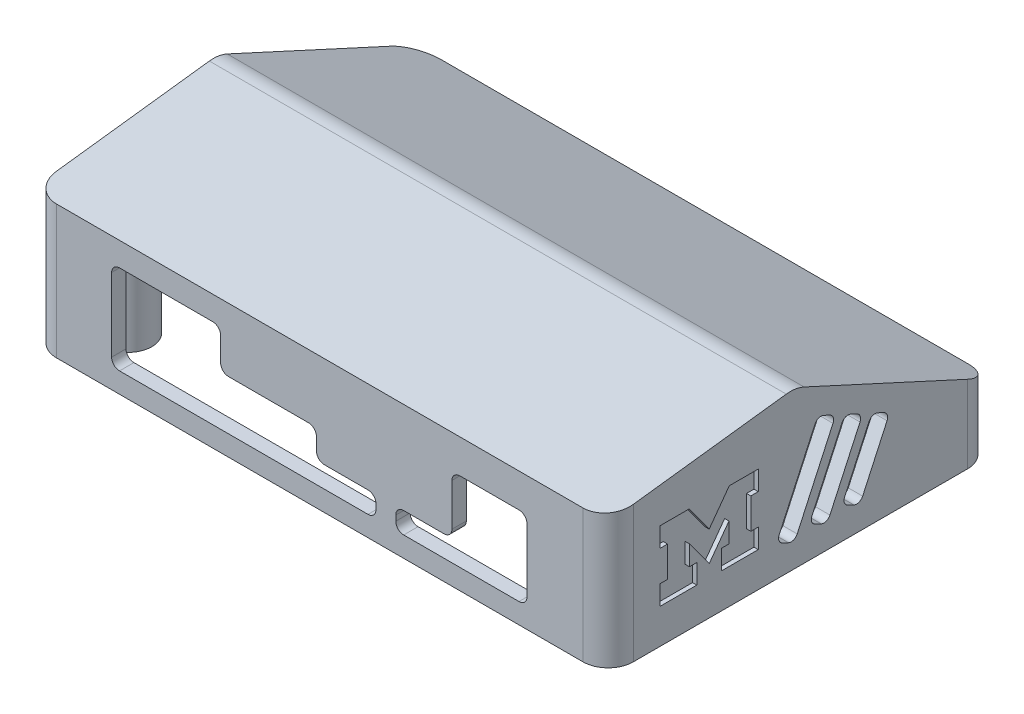
SolidWorks part; units mm, degrees
ref_plane "Front Plane" through (0, 0, 0) normal (0, 0, 1) x (1, 0, 0)
ref_plane "Top Plane" through (0, 0, 0) normal (0, 1, 0) x (1, 0, 0)
ref_plane "Right Plane" through (0, 0, 0) normal (1, 0, 0) x (0, 0, -1)
sketch "Sketch1" plane through (0, 0, 0) normal (0, 1, 0) x (1, 0, 0)
  line L0 (-37.7767, 21.1111) -> (-37.7767, -27.7389)
  line L1 (-34.6167, 23.6111) -> (43.3333, 23.6111)
  line L2 (-37.1167, 21.1111) -> (-37.1167, -27.7389)
  line L3 (-34.6167, -30.2389) -> (43.3333, -30.2389)
  line L4 (45.8333, 21.1111) -> (45.8333, -27.7389)
  line L5 (-34.6167, -30.8989) -> (43.3333, -30.8989)
  line L6 (46.4933, 21.1111) -> (46.4933, -27.7389)
  line L7 (-34.6167, 24.2711) -> (43.3333, 24.2711)
  arc A0 (-37.1167, -27.7389) -> (-34.6167, -30.2389) centre (-34.6167, -27.7389) ccw
  arc A1 (43.3333, -30.2389) -> (45.8333, -27.7389) centre (43.3333, -27.7389) ccw
  arc A2 (43.3333, 23.6111) -> (45.8333, 21.1111) centre (43.3333, 21.1111) cw
  arc A3 (-34.6167, 23.6111) -> (-37.1167, 21.1111) centre (-34.6167, 21.1111) ccw
  arc A4 (-37.7767, -27.7389) -> (-34.6167, -30.8989) centre (-34.6167, -27.7389) ccw
  arc A5 (43.3333, -30.8989) -> (46.4933, -27.7389) centre (43.3333, -27.7389) ccw
  arc A6 (43.3333, 24.2711) -> (46.4933, 21.1111) centre (43.3333, 21.1111) cw
  arc A7 (-34.6167, 24.2711) -> (-37.7767, 21.1111) centre (-34.6167, 21.1111) ccw
  point P8 (45.8333, -30.2389)
  point P11 (45.8333, 23.6111)
  point P14 (-37.1167, 23.6111)
  dimension "D3" = 2.5
  dimension "D1" = 82.95
  dimension "D2" = 53.85
  dimension "D4" = 0.66
extrude "Boss-Extrude1" add sketch "Sketch1" along normal blind 1.8
sketch "Sketch3" plane through (0, 1.8, 0) normal (0, 1, 0) x (1, 0, 0)
  line L8 (43.3333, 21.5611) -> (-34.6167, 21.5611)
  line L9 (-35.0667, 21.1111) -> (-35.0667, -27.7389)
  line L10 (-37.1167, 21.1111) -> (-37.1167, -27.7389)
  line L11 (-34.6167, -30.2389) -> (43.3333, -30.2389)
  line L33 (45.8333, -27.7389) -> (45.8333, 21.1111)
  line L34 (43.3333, 23.6111) -> (-34.6167, 23.6111)
  line L35 (-39.2917, 21.1111) -> (-39.2917, 25.7861)
  line L36 (-39.2917, 25.7861) -> (-34.6167, 25.7861)
  line L37 (43.3333, 25.7861) -> (-34.6167, 25.7861)
  line L38 (-39.2917, 21.1111) -> (-39.2917, -27.7389)
  line L39 (-34.6167, -32.4139) -> (43.3333, -32.4139)
  line L40 (48.0083, -27.7389) -> (48.0083, 21.1111)
  line L41 (43.3333, 25.7861) -> (-34.6167, 25.7861)
  line L42 (-39.2917, 21.1111) -> (-39.2917, -27.7389)
  line L43 (-34.6167, -32.4139) -> (43.3333, -32.4139)
  line L44 (48.0083, -27.7389) -> (48.0083, 21.1111)
  line L45 (-34.6167, 25.7861) -> (-34.5188, 25.7484)
  line L46 (48.0083, 21.1111) -> (48.0083, 25.7861)
  line L47 (48.0083, 25.7861) -> (43.3333, 25.7861)
  line L48 (43.3333, 25.7861) -> (43.4732, 25.7999)
  line L49 (48.0083, -27.7389) -> (48.0083, -32.4139)
  line L50 (48.0083, -32.4139) -> (43.3333, -32.4139)
  line L51 (-39.2917, -27.7389) -> (-39.2917, -32.4139)
  line L52 (-39.2917, -32.4139) -> (-34.6167, -32.4139)
  arc A6 (43.7833, 21.1111) -> (43.3333, 21.5611) centre (43.3333, 21.1111) ccw
  arc A7 (-34.6167, 21.5611) -> (-35.0667, 21.1111) centre (-34.6167, 21.1111) ccw
  arc A8 (43.7833, 21.1111) -> (43.3333, 21.5611) centre (43.3333, 21.1111) ccw
  arc A9 (-37.1167, -27.7389) -> (-34.6167, -30.2389) centre (-34.6167, -27.7389) ccw
  arc A21 (43.3333, -30.2389) -> (45.8333, -27.7389) centre (43.3333, -27.7389) ccw
  arc A22 (45.8333, 21.1111) -> (43.3333, 23.6111) centre (43.3333, 21.1111) ccw
  arc A23 (-34.6167, 23.6111) -> (-37.1167, 21.1111) centre (-34.6167, 21.1111) ccw
  arc A25 (43.3333, -32.4139) -> (48.0083, -27.7389) centre (43.3333, -27.7389) ccw
  arc A26 (48.0083, 21.1111) -> (43.3333, 25.7861) centre (43.3333, 21.1111) ccw
  arc A27 (-34.6167, 25.7861) -> (-39.2917, 21.1111) centre (-34.6167, 21.1111) ccw
  arc A28 (-39.2917, -27.7389) -> (-34.6167, -32.4139) centre (-34.6167, -27.7389) ccw
  arc A29 (43.3333, -32.4139) -> (48.0083, -27.7389) centre (43.3333, -27.7389) ccw
  arc A30 (48.0083, 21.1111) -> (43.3333, 25.7861) centre (43.3333, 21.1111) ccw
  arc A31 (-34.6167, 25.7861) -> (-39.2917, 21.1111) centre (-34.6167, 21.1111) ccw
  arc A32 (-39.2917, -27.7389) -> (-34.6167, -32.4139) centre (-34.6167, -27.7389) ccw
  arc M13 (-34.6167, 24.2711) -> (-37.7767, 21.1111) centre (-34.6167, 21.1111) ccw
  line M14 (-37.7767, 21.1111) -> (-37.7767, -27.7389)
  arc M15 (-37.7767, -27.7389) -> (-34.6167, -30.8989) centre (-34.6167, -27.7389) ccw
  line M16 (-34.6167, -30.8989) -> (43.3333, -30.8989)
  arc M17 (43.3333, -30.8989) -> (46.4933, -27.7389) centre (43.3333, -27.7389) ccw
  line M18 (46.4933, -27.7389) -> (46.4933, 21.1111)
  arc M19 (46.4933, 21.1111) -> (43.3333, 24.2711) centre (43.3333, 21.1111) ccw
  line M20 (43.3333, 24.2711) -> (-34.6167, 24.2711)
  line M21 (43.3333, -30.2389) -> (-34.6167, -30.2389)
  arc M22 (-34.6167, -30.2389) -> (-37.1167, -27.7389) centre (-34.6167, -27.7389) cw
  line M23 (-37.1167, -27.7389) -> (-37.1167, 21.1111)
  arc M24 (-37.1167, 21.1111) -> (-34.6167, 23.6111) centre (-34.6167, 21.1111) cw
  line M25 (-34.6167, 23.6111) -> (43.3333, 23.6111)
  arc M26 (43.3333, 23.6111) -> (45.8333, 21.1111) centre (43.3333, 21.1111) cw
  line M27 (45.8333, 21.1111) -> (45.8333, -27.7389)
  arc M28 (45.8333, -27.7389) -> (43.3333, -30.2389) centre (43.3333, -27.7389) cw
  dimension "D1" = 2.05
  dimension "D2" = 2.175
  dimension "D3" = 2.175
extrude "Boss-Extrude3" add sketch "Sketch3" along normal blind 10 contours L42 A32 L43 A29 L44 A30 L41 A31 M13 M20 M19 M18 M17 M16 M15 M14 | A32 L51 L52 | M20 M13 M14 M15 M16 M17 M18 M19 M28 M21 M22 M23 M24 M25 M26 M27 | A31 L36 L35 | A30 L46 L47 | A29 L50 L49 region at (-37.1805, 1.8, -23.6749) region at (-38.2474, 1.8, -24.7419) region at (-38.2474, 1.8, 31.3696) region at (46.9641, 1.8, -24.7419) region at (46.9641, 1.8, 31.3696) region at (4.3583, 1.8, -24.1704)
sketch "Sketch4" plane through (0, 0, -25.7861) normal (0, 0, -1) x (-1, 0, 0)
  line L0 (-4.3583, 1.8) -> (-4.3583, 25.0723)
  line L1 (-48.0083, 1.8) -> (39.2917, 1.8) construction
  line L2 (7.9607, 1.8) -> (7.9607, 25.0723)
  line L3 (20.6617, 1.8) -> (20.6617, 22.638)
  line L4 (7.9607, 5.44) -> (20.6617, 5.44)
  line L5 (4.5182, 1.8) -> (4.5182, -0.6587)
  line L6 (11.4031, 1.8) -> (11.4031, -0.6587)
  line L7 (11.4031, -0.6587) -> (4.5182, -0.6587)
  line L8 (17.2192, 1.8) -> (17.2192, -1.5181)
  line L9 (24.1041, -1.5181) -> (17.2192, -1.5181)
  line L10 (24.1041, 1.8) -> (24.1041, -1.5181)
  line L11 (-48.0083, 1.8) -> (39.2917, 1.8) construction
  circle A0 centre (7.9607, 5.44) radius 5.01
  circle A1 centre (20.6617, 5.44) radius 5.01
  line M1 (-48.0083, 1.8) -> (39.2917, 1.8)
  dimension "D4" = 10.02
  dimension "D5" = 10.02
  dimension "D2" = 25.02
  dimension "D3" = 3.64
  dimension "D1" = 12.319
extrude "Cut-Extrude1" cut sketch "Sketch4" against normal blind 5 contours L2 A0 M1 | A0 L4 L2 M1 | L4 A0 L2 | A0 L5 L7 L6 | A0 M1 | A1 L8 L9 L10 | A1 region at (-5.762, 5.8158, -25.7861) region at (-7.9607, 1.245, -25.7861) region at (-10.246, 3.7208, -25.7861) region at (-10.087, 7.5663, -25.7861) region at (-7.9607, 0.1521, -25.7861) region at (-20.6617, -0.2965, -25.7861)
sketch "Sketch5" plane through (0, 0, -25.7861) normal (0, 0, -1) x (-1, 0, 0)
  line L0 (-4.3583, 11.8) -> (-4.3583, -7.2365)
  line L1 (-48.0083, 11.8) -> (39.2917, 11.8) construction
  line L2 (-17.3383, 11.8) -> (-17.3383, -7.2365)
  line L3 (-48.0083, 1.8) -> (4.5182, 1.8) construction
  line L5 (-17.3383, 1.8) -> (-17.3383, 8.55)
  line L6 (-17.3383, 8.55) -> (-10.9347, 8.55)
  line L8 (-4.6583, 11.8) -> (-4.6583, -7.2365)
  line L9 (-4.6583, 8.55) -> (-7.6243, 8.55)
  circle A0 centre (-17.3383, 8.55) radius 1.69
  circle A1 centre (-17.3383, 8.55) radius 2.19
  circle A2 centre (-4.6583, 8.55) radius 1.69
  circle A3 centre (-4.6583, 8.55) radius 2.19
  dimension "D3" = 3.38
  dimension "D6" = 3.38
  dimension "D2" = 6.75
  dimension "D1" = 12.98
  dimension "D4" = 0.5
  dimension "D5" = 0.3
  dimension "D7" = 0.5
extrude "Cut-Extrude2" cut sketch "Sketch5" against normal blind 5 contours A3 | A1
sketch "Sketch6" plane through (0, 11.8, 0) normal (0, 1, 0) x (1, 0, 0)
  line L0 (-37.1167, -3.3139) -> (-39.2917, -3.3139)
  line L2 (-37.1167, -27.7389) -> (-37.1167, 21.1111) construction
  line L3 (-37.1167, -3.3139) -> (45.8333, -3.3139)
  line L4 (45.8333, 21.1111) -> (45.8333, -27.7389) construction
  line L5 (45.8333, -3.3139) -> (48.0083, -3.3139)
  line L19 (48.0083, -28.6139) -> (48.0083, -32.4139)
  line L20 (48.0083, -32.4139) -> (44.2083, -32.4139)
  line L21 (-39.2917, -28.6139) -> (-39.2917, -32.4139)
  line L22 (48.0083, -28.6139) -> (48.0083, 25.7861)
  line L23 (-35.4917, -32.4139) -> (44.2083, -32.4139)
  line L24 (-39.2917, 25.7861) -> (-39.2917, -28.6139)
  line L31 (-39.2917, -32.4139) -> (-35.4917, -32.4139)
  line L37 (45.8333, 21.1111) -> (45.8333, -27.7389)
  line L38 (43.3333, -30.2389) -> (-34.6167, -30.2389)
  line L39 (-37.1167, -27.7389) -> (-37.1167, 21.1111)
  arc A20 (43.3333, -30.2389) -> (45.8333, -27.7389) centre (43.3333, -27.7389) ccw
  arc A21 (-37.1167, -27.7389) -> (-34.6167, -30.2389) centre (-34.6167, -27.7389) ccw
  line M11 (-39.2917, 25.7861) -> (-39.2917, -32.4139)
  line M13 (-39.2917, -32.4139) -> (48.0083, -32.4139)
  line M15 (48.0083, -32.4139) -> (48.0083, 25.7861)
  arc M19 (45.8333, -27.7389) -> (43.3333, -30.2389) centre (43.3333, -27.7389) cw
  line M20 (43.3333, -30.2389) -> (-34.6167, -30.2389)
  arc M21 (-34.6167, -30.2389) -> (-37.1167, -27.7389) centre (-34.6167, -27.7389) cw
  line M22 (-37.1167, -27.7389) -> (-37.1167, 21.1111)
  line M26 (45.8333, 21.1111) -> (45.8333, -27.7389)
  dimension "D3" = 29.1
extrude "Boss-Extrude4" add sketch "Sketch6" along normal blind 8 contours M26 M19 M20 M21 M22 M11 M13 M15 region at (-38.0369, 11.8, 15.5264)
sketch "Sketch7" plane through (0, 19.8, 0) normal (0, 1, 0) x (1, 0, 0)
  line L0 (-39.2917, -30.2389) -> (48.0083, -30.2389)
  line L1 (48.0083, -31.3688) -> (48.0083, -32.4139)
  line L2 (48.0083, -32.4139) -> (44.2083, -32.4139)
  line L3 (-39.2917, -31.3688) -> (-39.2917, -32.4139)
  line L4 (-39.2917, -32.4139) -> (-35.4917, -32.4139)
  line L8 (43.3333, -30.2389) -> (-34.6167, -30.2389) construction
  line L9 (-39.2917, -3.3139) -> (-39.2917, -32.4139) construction
  line L10 (48.0083, -32.4139) -> (48.0083, -3.3139) construction
  line L19 (-35.4917, -32.4139) -> (44.2083, -32.4139)
  line L20 (-39.2917, -30.2389) -> (-39.2917, -31.3688)
  line L21 (48.0083, -31.3688) -> (48.0083, -30.2389)
  dimension "D1" = 2.175
  dimension "D2" = 2.175
extrude "Boss-Extrude5" add sketch "Sketch7" along normal blind 2.175
sketch "Sketch15" plane through (0, 0, 32.4139) normal (0, 0, 1) x (1, 0, 0)
  line L0 (4.3583, 4.8675) -> (4.3583, 8.0675)
  line L1 (-39.2917, 1.8) -> (48.0083, 1.8) construction
  line L2 (-39.2917, 21.975) -> (48.0083, 21.975) construction
  line L3 (-27.1327, 4.8675) -> (12.8673, 4.8675)
  line L4 (-27.1327, 4.8675) -> (12.8673, 4.8675)
  line L6 (-18.8827, 4.8675) -> (-18.8827, 18.3675)
  line L7 (-10.6327, 4.8675) -> (-10.6327, 18.3675)
  line L8 (-27.1327, 4.8675) -> (-27.1327, 18.3675)
  line L9 (-27.1327, 18.3675) -> (-10.6327, 18.3675)
  line L10 (4.3583, 18.3675) -> (48.0083, 18.3675)
  line L11 (-39.2917, 18.3675) -> (48.0083, 18.3675) construction
  line L12 (-27.1327, 1.8) -> (-27.1327, 21.975) construction
  line L13 (-10.6327, 1.8) -> (-10.6327, 21.975) construction
  line L14 (3.8673, 4.8675) -> (3.8673, 12.3675)
  line L15 (-10.6327, 12.3675) -> (3.8673, 12.3675)
  line L16 (12.8673, 4.8675) -> (12.8673, 8.0675)
  line L17 (3.8673, 4.8675) -> (3.8673, 18.3675) construction
  line L18 (3.8673, 8.0675) -> (12.8673, 8.0675)
  line L19 (15.8673, 4.8675) -> (15.8673, 8.0675)
  line L20 (12.8673, 4.8675) -> (12.8673, 12.3675) construction
  line L22 (15.8673, 8.0675) -> (24.3673, 8.0675)
  line L23 (30.4695, 4.8675) -> (30.4695, 16.8675)
  line L24 (35.7195, 4.8675) -> (35.7195, 16.8675)
  line L26 (25.2195, 16.8675) -> (35.7195, 16.8675)
  line L27 (25.2195, 18.3675) -> (25.2195, 21.975)
  line L28 (35.7195, 18.3675) -> (35.7195, 21.975)
  line L30 (4.3583, 18.3675) -> (4.3583, 21.975)
  line L31 (35.7195, 1.8) -> (35.7195, 21.975) construction
  line L32 (-18.8827, 1.8) -> (-18.8827, 21.975) construction
  line L33 (-39.2917, 4.8675) -> (48.0083, 4.8675) construction
  line L34 (25.2195, 4.8675) -> (35.7195, 4.8675)
  line L35 (4.3583, 1.8) -> (4.3583, 21.975) construction
  line L36 (30.4695, 1.8) -> (30.4695, 21.975) construction
  line L37 (15.8673, 4.8675) -> (24.3673, 4.8675)
  line L38 (30.4695, 18.3675) -> (30.4695, 21.975)
  line L39 (-27.1327, 4.8675) -> (-27.1327, 18.3675)
  line L40 (-10.6327, 18.3675) -> (-10.6327, 12.3675)
  line L41 (3.8673, 12.3675) -> (3.8673, 8.0675)
  line L42 (15.8673, 4.8675) -> (24.3673, 4.8675)
  line L44 (35.7195, 16.8675) -> (35.7195, 4.8675)
  line L45 (25.2195, 4.8675) -> (35.7195, 4.8675)
  line L46 (25.2195, 16.8675) -> (24.3673, 16.8675)
  line L47 (24.3673, 16.8675) -> (24.3673, 8.0675)
  line L48 (24.3673, 4.8675) -> (25.2195, 4.8675)
  point P41 (25.2195, 1.8)
  dimension "D1" = 3.0675
  dimension "D7" = 7.5
  dimension "D9" = 3.2
  dimension "D15" = 12
  dimension "D2" = 23.241
  dimension "D3" = 8.25
  dimension "D4" = 8.25
  dimension "D5" = 13.5
  dimension "D6" = 14.5
  dimension "D8" = 9
  dimension "D10" = 3
  dimension "D12" = 26.1112
  dimension "D13" = 5.25
extrude "Cut-Extrude3" cut sketch "Sketch15" against normal blind 2.175 contours L9 L8 L3 L6 | L9 L6 L4 L7 | L15 L7 L3 L14 | L18 L0 L3 L16 | L18 L14 L4 L0 | L19 L37 L22 | L34 L23 L26 | L23 L34 L24 L26 region at (4.1128, 6.4675, 32.4139) region at (8.6128, 6.4675, 32.4139) region at (-3.3827, 8.6175, 32.4139) region at (-14.7577, 11.6175, 32.4139) region at (-23.0077, 11.6175, 32.4139) region at (25.441, 9.6758, 32.4139) region at (33.0945, 10.8675, 32.4139)
sketch "Sketch24" plane through (-39.2917, 0, 0) normal (-1, 0, 0) x (0, 0, 1)
  line L0 (32.146, 19.8166) -> (4.3973, 23.2604)
  line L1 (4.3973, 23.2604) -> (-20.572, 11.8)
  line L2 (32.146, 19.8166) -> (32.4139, 19.8166)
  line L3 (32.4139, 21.975) -> (32.4139, 1.8) construction
  line L4 (32.4139, 19.8166) -> (32.4139, 21.975)
  line L5 (-25.7861, 11.8) -> (-20.572, 11.8)
  line L10 (4.3973, 23.2604) -> (-24.8788, 9.8233) construction
  line L23 (32.4139, 21.975) -> (4.0518, 25.495)
  line L24 (4.0518, 25.495) -> (-25.7861, 11.8)
  dimension "D1" = 2.175
extrude "Boss-Extrude11" add sketch "Sketch24" against normal up to surface (87.3 mm away) up to face at (48.0083, 14.4797, 13.5467)
sketch "Sketch28" plane through (-39.2917, 0, 0) normal (-1, 0, 0) x (0, 0, 1)
  line L0 (-20.572, 11.8) -> (4.3973, 23.2604)
  line L1 (4.3973, 23.2604) -> (30.2389, 20.0533)
  line L2 (30.2389, 20.0533) -> (30.2389, 19.8)
  line L3 (30.2389, 19.8) -> (3.3139, 19.8)
  line L4 (3.3139, 19.8) -> (3.3139, 11.8)
  line L5 (3.3139, 11.8) -> (-20.572, 11.8)
extrude "Boss-Extrude12" add sketch "Sketch28" against normal blind 2.175
sketch "Sketch29" plane through (48.0083, 0, 0) normal (1, 0, 0) x (0, 0, -1)
  line L0 (-30.2389, 20.0533) -> (-30.2389, 19.8)
  line L1 (-30.2389, 19.8) -> (-3.3139, 19.8)
  line L2 (-3.3139, 19.8) -> (-3.3139, 11.8)
  line L3 (-3.3139, 11.8) -> (20.572, 11.8)
  line L4 (20.572, 11.8) -> (-4.3973, 23.2604)
  line L5 (-4.3973, 23.2604) -> (-30.2389, 20.0533)
extrude "Boss-Extrude13" add sketch "Sketch29" against normal blind 2.175
sketch "Sketch32" plane through (48.0083, 0, 0) normal (1, 0, 0) x (0, 0, -1)
  line L0 (0.7555, 23.2886) -> (-6.9465, 6.5079)
  line L1 (25.7861, 11.8) -> (-4.0518, 25.495) construction
  line L2 (-6.9465, 6.5079) -> (-4.22, 5.2564)
  line L3 (-4.22, 5.2564) -> (2.0259, 18.8647)
  line L4 (2.0259, 18.8647) -> (-0.7006, 20.1161)
  line L5 (-2.8567, 4.6307) -> (-2.5695, 5.2564)
  line L7 (-1.9952, 6.5079) -> (3.3892, 18.239)
  line L8 (0.7314, 5.2564) -> (6.1157, 16.9876)
  line L9 (0.7314, 5.2564) -> (-1.9952, 6.5079)
  line L10 (-0.1302, 3.3793) -> (6.1157, 16.9876) construction
  line L12 (-2.8567, 4.6307) -> (3.3892, 18.239) construction
  line L14 (5.6827, 5.2564) -> (10.2055, 15.1104)
  line L16 (6.1157, 16.9876) -> (3.3892, 18.239)
  line L17 (7.479, 16.3618) -> (10.2055, 15.1104)
  line L18 (5.6827, 5.2564) -> (2.9562, 6.5079)
  line L19 (2.9562, 6.5079) -> (7.479, 16.3618)
  point P11 (2.0946, 4.6307)
  point P16 (3.4579, 4.005)
  point P17 (8.8422, 15.7361)
  point P18 (4.8211, 3.3793)
  dimension "D1" = 3
  dimension "D2" = 1.5
  dimension "D3" = 3
extrude "Cut-Extrude6" cut sketch "Sketch32" against normal through all contours L3 L4 L0 L2 | L8 L16 L7 L9 | L19 L18 L14 L17 region at (48.0083, 12.6863, 2.4603) region at (48.0083, 11.7477, -2.0603) region at (48.0083, 10.8091, -6.5808)
fillet "Fillet7" radius 1 24 edges at (46.9208, 5.2564, 4.22) (46.9208, 5.2564, -0.7314) (46.9208, 5.2564, -5.6827) (46.9208, 18.8647, -2.0259) (46.9208, 16.9876, -6.1157) (46.9208, 15.1104, -10.2055) (46.9208, 6.5079, 6.9465) (46.9208, 6.5079, 1.9952) (46.9208, 6.5079, -2.9562) (46.9208, 16.3618, -7.479) (46.9208, 20.1161, 0.7006) (46.9208, 18.239, -3.3892) (-38.2042, 16.9876, -6.1157) (-38.2042, 18.8647, -2.0259) (-38.2042, 15.1104, -10.2055) (-38.2042, 5.2564, -5.6827) (-38.2042, 5.2564, -0.7314) (-38.2042, 6.5079, -2.9562) (-38.2042, 6.5079, 1.9952) (-38.2042, 6.5079, 6.9465) (-38.2042, 16.3618, -7.479) (-38.2042, 18.239, -3.3892) (-38.2042, 20.1161, 0.7006) (-38.2042, 5.2564, 4.22)
fillet "Fillet1" radius 3.8 2 edges at (-39.2917, 11.8875, 32.4139) (48.0083, 11.8875, 32.4139)
fillet "Fillet2" radius 3.8 2 edges at (-39.2917, 6.8, -25.7861) (48.0083, 6.8, -25.7861)
fillet "Fillet4" radius 1.2 14 edges at (15.8673, 4.8675, 31.3264) (35.7195, 4.8675, 31.3264) (12.8673, 4.8675, 31.3264) (15.8673, 8.0675, 31.3264) (35.7195, 16.8675, 31.3264) (3.8673, 8.0675, 31.3264) (12.8673, 8.0675, 31.3264) (3.8673, 12.3675, 31.3264) (-10.6327, 18.3675, 31.3264) (-10.6327, 12.3675, 31.3264) (-27.1327, 18.3675, 31.3264) (-27.1327, 4.8675, 31.3264) (24.3673, 16.8675, 31.3264) (24.3673, 8.0675, 31.3264)
fillet "Fillet6" [suppressed] radius 1.5
sketch "Sketch20" plane through (0, 0, 0) normal (0, -1, 0) x (1, 0, 0)
  line L2 (-31.9917, -18.4361) -> (-37.1167, -18.4361) construction
  line L3 (-37.1167, -21.1111) -> (-37.1167, 27.7389) construction
  line L4 (40.7083, -18.4361) -> (45.8333, -18.4361) construction
  line L5 (45.8333, 27.7389) -> (45.8333, -21.1111) construction
  line L6 (-31.9917, 25.0639) -> (-31.9917, 30.2389) construction
  line L7 (-34.6167, 30.2389) -> (43.3333, 30.2389) construction
  line L8 (-31.9917, -18.4361) -> (-31.9917, -23.6111) construction
  line L9 (-24.1041, -23.6111) -> (-34.6167, -23.6111) construction
  circle A0 centre (-31.9917, -18.4361) radius 3.6
  circle A1 centre (-31.9917, -18.4361) radius 2
  circle A2 centre (40.7083, -18.4361) radius 2
  circle A3 centre (40.7083, -18.4361) radius 3.6
  circle A4 centre (40.7083, 25.0639) radius 2
  circle A5 centre (40.7083, 25.0639) radius 3.6
  circle A6 centre (-31.9917, 25.0639) radius 2
  circle A7 centre (-31.9917, 25.0639) radius 3.6
  dimension "D1" = 7.2
  dimension "D2" = 4
  dimension "D5" = 72.7
  dimension "D6" = 43.5
  dimension "D3" = 2
  dimension "D4" = 2
extrude "Boss-Extrude9" add sketch "Sketch20" against normal up to surface (18.0123 mm away) from offset 3.13 contours A5 A4 | A7 A6 region at (37.2102, 0, 25.0639) region at (-35.4898, 0, 25.0639) up to face at (4.3583, 21.6568, 17.3181) offset against normal yes
sketch "Sketch22" plane through (-39.2917, 0, 0) normal (-1, 0, 0) x (0, 0, 1)
  line L0 (28.6139, 1.8) -> (37.2656, 1.8)
  line L1 (37.2656, 1.8) -> (37.2656, 0)
  line L2 (37.2656, 0) -> (-27.0337, 0)
  line L3 (-27.0337, 0) -> (-27.0337, 1.8)
  line L4 (-27.0337, 1.8) -> (28.6139, 1.8)
extrude "Cut-Extrude4" cut sketch "Sketch22" against normal through all
sketch "Sketch23" plane through (-39.2917, 0, 0) normal (-1, 0, 0) x (0, 0, 1)
  line L0 (3.3139, 1.8) -> (3.3139, 3.3)
  line L1 (-21.9861, 1.8) -> (28.6139, 1.8) construction
  line L2 (3.3139, 3.3) -> (-5.2861, 3.3)
  line L3 (-5.2861, 3.3) -> (-5.2861, 1.8)
  line L4 (-5.2861, 1.8) -> (7.2139, 1.8)
  line L5 (7.2139, 1.8) -> (7.2139, 3.3)
  line L6 (7.2139, 3.3) -> (3.3139, 3.3)
  line M4 (-21.9861, 1.8) -> (28.6139, 1.8)
  dimension "D1" = 1.5
  dimension "D2" = 8.6
  dimension "D3" = 12.5
extrude "Cut-Extrude5" cut sketch "Sketch23" against normal blind 2.175 contours L2 L3 L0 M4 | L5 L6 L0 M4 region at (-39.2917, 2.55, -0.9861) region at (-39.2917, 2.55, 5.2639)
extrude "Boss-Extrude14" add sketch "Sketch20<4>" against normal up to next from offset 3.13 contours A3 A2 | A0 A1 region at (-35.4898, 0, -18.4361) region at (37.2102, 0, -18.4361) offset against normal yes
sketch "Sketch20<4>" plane through (0, 0, 0) normal (0, -1, 0) x (1, 0, 0) same geometry as "Sketch20"
fillet "Fillet8" radius 5 1 edges at (4.3583, 25.495, 4.0518)
sketch "Sketch33" plane through (48.0083, 0, 0) normal (1, 0, 0) x (0, 0, -1)
  line L0 (-24.5468, 17.6178) -> (-24.5468, 14.6578)
  line L1 (-24.5468, 14.6578) -> (-23.4268, 14.6578)
  line L2 (-23.4268, 14.6578) -> (-23.4268, 10.0178)
  line L3 (-23.4268, 10.0178) -> (-24.5468, 10.0178)
  line L4 (-24.5468, 10.0178) -> (-24.5468, 7.0578)
  line L5 (-24.5468, 7.0578) -> (-18.9948, 7.0578)
  line L6 (-18.9948, 7.0578) -> (-18.9948, 10.0178)
  line L7 (-18.9948, 10.0178) -> (-20.1148, 10.0178)
  line L8 (-20.1148, 10.0178) -> (-20.1148, 13.0258)
  line L9 (-20.1148, 13.0258) -> (-17.1228, 8.9315)
  line L11 (-17.1228, 13.4578) -> (-14.0828, 17.6178)
  line L12 (-14.1308, 13.0258) -> (-17.1228, 8.9315)
  line L13 (-14.0828, 17.6178) -> (-9.6988, 17.6178)
  line L14 (-14.1308, 10.0178) -> (-14.1308, 13.0258)
  line L15 (-15.2508, 10.0178) -> (-14.1308, 10.0178)
  line L16 (-15.2508, 7.0578) -> (-15.2508, 10.0178)
  line L17 (-9.6988, 7.0578) -> (-15.2508, 7.0578)
  line L18 (-9.6988, 10.0178) -> (-9.6988, 7.0578)
  line L19 (-10.8188, 10.0178) -> (-9.6988, 10.0178)
  line L20 (-10.8188, 14.6578) -> (-10.8188, 10.0178)
  line L21 (-9.6988, 14.6578) -> (-10.8188, 14.6578)
  line L22 (-17.1228, 13.4578) -> (-20.1628, 17.6178)
  line L23 (-20.1628, 17.6178) -> (-24.5468, 17.6178)
  line L24 (-9.6988, 17.6178) -> (-9.6988, 14.6578)
extrude "Cut-Extrude7" cut sketch "Sketch33" against normal blind 0.65
